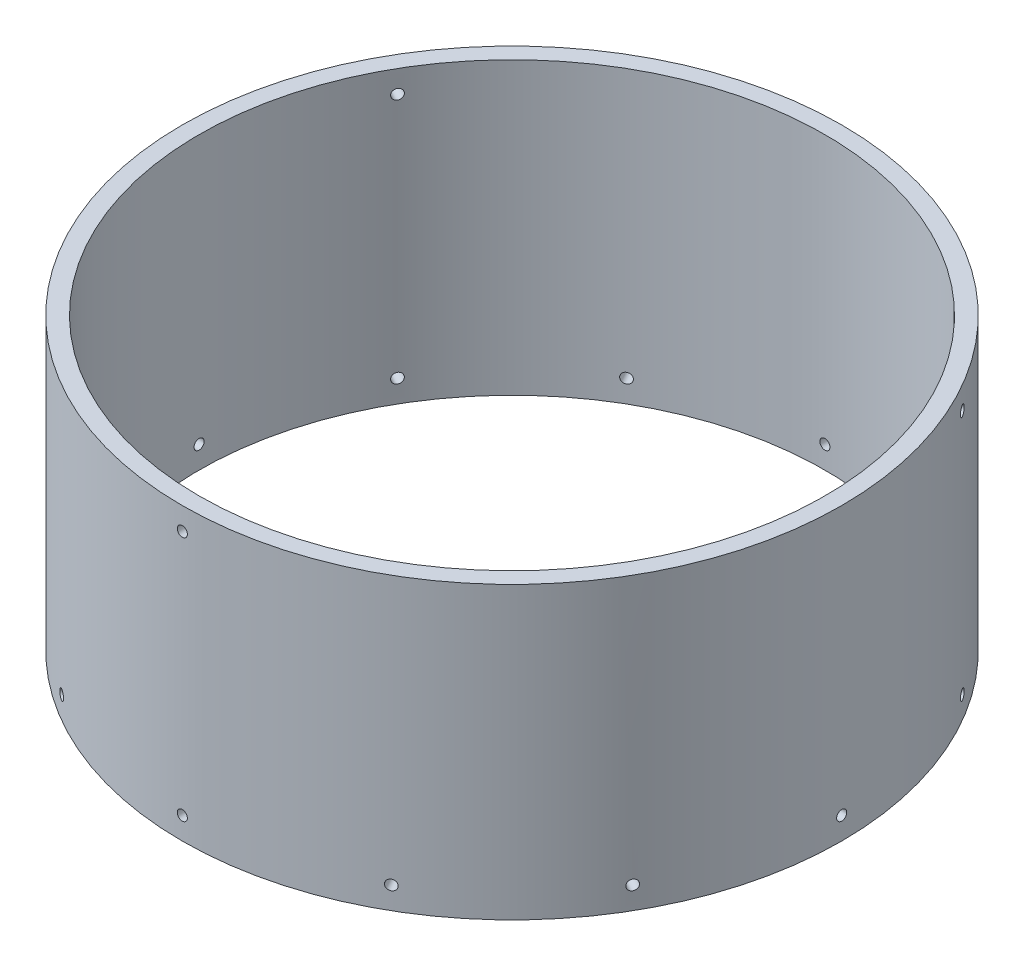
SolidWorks part; units mm, degrees
material "PVC Rigid"
ref_plane "Front Plane" through (0, 0, 0) normal (0, 0, 1) x (1, 0, 0)
ref_plane "Top Plane" through (0, 0, 0) normal (0, 1, 0) x (1, 0, 0)
ref_plane "Right Plane" through (0, 0, 0) normal (1, 0, 0) x (0, 0, -1)
sketch "Sketch1" plane through (0, 0, 0) normal (0, 1, 0) x (1, 0, 0)
  circle A0 centre (0, 0) radius 93.6625
  circle A1 centre (0, 0) radius 88.9
  dimension "D1" = 187.325
  dimension "D2" = 177.8
extrude "Boss-Extrude1" add sketch "Sketch1" along normal mid plane 82.55
ref_plane "Plane1" through (0, 0, 93.6625) normal (0, 0, 1) x (1, 0, 0)
sketch "Sketch2" plane through (0, 0, 93.6625) normal (0, 0, 1) x (1, 0, 0)
  line L0 (0, -45.4025) -> (0, 45.4025) construction
  line L1 (-93.6625, -41.275) -> (93.6625, -41.275) construction
  circle A0 centre (0, -34.925) radius 1.4351
  dimension "D1" = 2.8702
  dimension "D2" = 6.35
extrude "Cut-Extrude1" cut sketch "Sketch2" against normal blind 25.146
pattern_circular "CirPattern1" count 12 over 360 about axis through (0, 41.275, 0) along (0, -1, 0) of "Cut-Extrude1" reverse direction yes
sketch "Sketch3" plane through (0, 0, 93.6625) normal (0, 0, 1) x (1, 0, 0)
  line L0 (0, -45.4025) -> (0, 45.4025) construction
  line L1 (88.9, 41.275) -> (-88.9, 41.275) construction
  circle A1 centre (0, 34.925) radius 1.4351
  dimension "D1" = 2.8702
  dimension "D3" = 6.35
extrude "Cut-Extrude2" cut sketch "Sketch3" against normal blind 25.908
pattern_circular "CirPattern2" count 3 over 360 about axis through (0, 41.275, 0) along (0, -1, 0) of "Cut-Extrude2"
